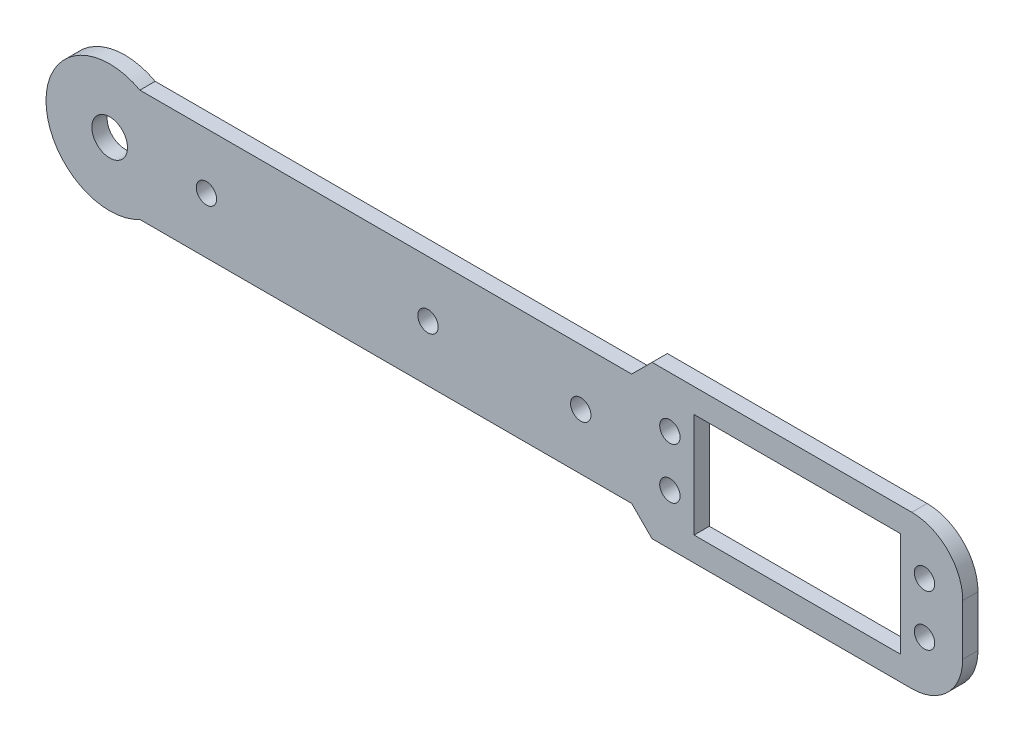
SolidWorks part; units mm, degrees
material "Balsa"
ref_plane "Alzado" through (0, 0, 0) normal (0, 0, 1) x (1, 0, 0)
ref_plane "Planta" through (0, 0, 0) normal (0, 1, 0) x (1, 0, 0)
ref_plane "Vista lateral" through (0, 0, 0) normal (1, 0, 0) x (0, 0, -1)
sketch "Croquis1" plane through (0, 0, 0) normal (0, 0, 1) x (1, 0, 0)
  line L4 (90, -15) -> (90, 15)
  line L9 (-25, 11) -> (25, 11)
  line L10 (25, 15) -> (25, 11)
  line L11 (25, -15) -> (90, -15)
  line L14 (25, -15) -> (25, -11)
  line L15 (-25, -11) -> (25, -11)
  line L16 (25, 15) -> (90, 15)
  line L17 (-25, 11) -> (-71.5628, 11)
  line L19 (-25, -11) -> (-71.5628, -11)
  arc A0 (-71.5628, 11) -> (-71.5628, -11) centre (-77.5, 0) ccw
  point P0 (0, 0)
  point P8 (0, 15)
  dimension "D3" = 50
  dimension "D1" = 12.5
  dimension "D2" = 30
  dimension "D4" = 77.5
  dimension "D5" = 4
  dimension "D6" = 11
extrude "Saliente-Extruir1" add sketch "Croquis1" along normal blind 3
fillet "Redondeo1" radius 10 2 edges at (90, -15, 1.5) (90, 15, 1.5)
chamfer "Chaflán1" distance 4 angle 45 2 edges at (25, -15, 1.5) (25, 15, 1.5)
sketch "Croquis2" plane through (0, 0, 3) normal (0, 0, 1) x (1, 0, 0)
  line L0 (90, -5) -> (90, 5) construction
  line L1 (37.25, 10.25) -> (77.75, 10.25)
  line L2 (37.25, 10.25) -> (37.25, -10.25)
  line L3 (37.25, -10.25) -> (77.75, -10.25)
  line L4 (77.75, 10.25) -> (77.75, -10.25)
  line L5 (37.25, 10.25) -> (77.75, -10.25) construction
  line L6 (37.25, -10.25) -> (77.75, 10.25) construction
  line L7 (80, 15) -> (29, 15) construction
  line L8 (57.5, 0) -> (49.6153, 0) construction
  line L9 (49.6153, 0) -> (57.5, 0) construction
  line L10 (57.5, 0) -> (57.5, 5) construction
  circle A0 centre (82.5, 5) radius 2
  circle A1 centre (32.5, 5) radius 2
  circle A2 centre (82.5, -5) radius 2
  circle A3 centre (32.5, -5) radius 2
  point P0 (57.5, 0)
  dimension "D5" = 5
  dimension "D1" = 40.5
  dimension "D2" = 20.5
  dimension "D3" = 32.5
  dimension "D4" = 15
  dimension "D6" = 25
extrude "Cortar-Extruir1" cut sketch "Croquis2" against normal up to next
sketch "Croquis3" plane through (0, 0, 3) normal (0, 0, 1) x (1, 0, 0)
  line L0 (-71.5628, -11) -> (25, -11) construction
  circle A0 centre (-77.5, 0) radius 3.5
  arc A1 (-71.5628, 11) -> (-71.5628, -11) centre (-77.5, 0) ccw construction
  circle A2 centre (-58.5, 0) radius 2
  point P5 (-90, 0)
  dimension "D1" = 12.5
  dimension "D2" = 19
  dimension "D3" = 11
extrude "Cortar-Extruir2" cut sketch "Croquis3" against normal up to next
sketch "Croquis4" plane through (0, 0, 3) normal (0, 0, 1) x (1, 0, 0)
  circle A0 centre (-15, 0) radius 2
  circle A2 centre (15, 0) radius 2
  dimension "D1" = 15
  dimension "D2" = 30
extrude "Cortar-Extruir3" cut sketch "Croquis4" against normal up to next
